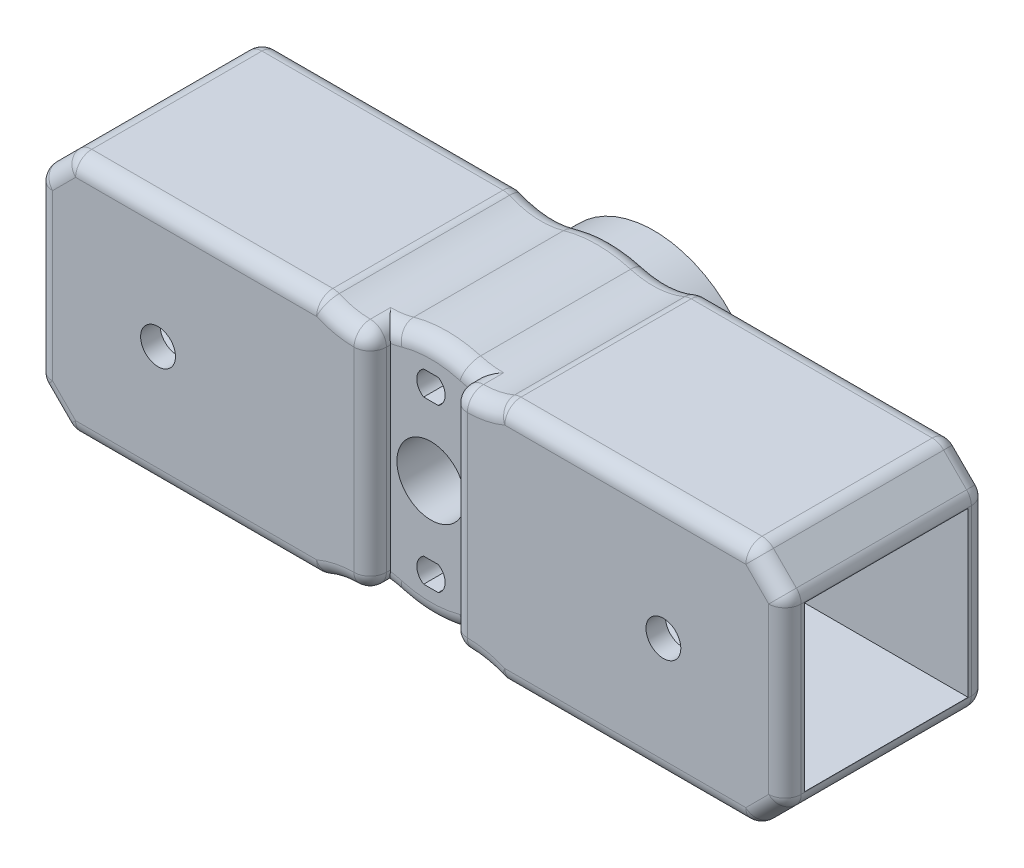
SolidWorks part; units mm, degrees
ref_plane "Alzado" through (0, 0, 0) normal (0, 0, 1) x (1, 0, 0)
ref_plane "Planta" through (0, 0, 0) normal (0, 1, 0) x (1, 0, 0)
ref_plane "Vista lateral" through (0, 0, 0) normal (1, 0, 0) x (0, 0, -1)
sketch "Croquis1" plane through (0, 0, 0) normal (0, 0, 1) x (1, 0, 0)
  circle A0 centre (0, 0) radius 15
  circle A1 centre (0, 0) radius 11.1
  dimension "D1" = 30
  dimension "D2" = 22.2
extrude "Saliente-Extruir1" add sketch "Croquis1" along normal mid plane 25
sketch "Croquis10" plane through (0, 0, 12.5) normal (0, 0, 1) x (1, 0, 0)
  line L0 (11.1803, 0) -> (-11.1803, 0) construction
  line L1 (0, 0) -> (0, 10.6419) construction
  line L2 (-11.1803, -15) -> (-11.1803, 15)
  line L3 (-11.1803, 15) -> (-46.1803, 15)
  line L4 (-46.1803, 15) -> (-46.1803, -15)
  line L5 (-46.1803, -15) -> (-11.1803, -15)
  line L6 (46.1803, 15) -> (46.1803, -15)
  line L7 (11.1803, 15) -> (46.1803, 15)
  line L8 (11.1803, -15) -> (11.1803, 15)
  line L9 (46.1803, -15) -> (11.1803, -15)
  line L10 (-11.1803, 0) -> (-46.1803, 0) construction
  circle A1 centre (-31.1803, 0) radius 2.15
  circle A2 centre (31.1803, 0) radius 2.15
  point P5 (0, 0)
  point P13 (-11.1803, 0)
  dimension "D3" = 4.3
  dimension "D1" = 35
  dimension "D2" = 30
  dimension "D4" = 15
extrude "Saliente-Extruir8" add sketch "Croquis10" against normal blind 25
sketch "Croquis11" plane through (0, 0, -12.5) normal (0, 0, 1) x (1, 0, 0)
  line L6 (0, 0) -> (0, 7.4469) construction
  line L7 (16.1803, -10) -> (36.1803, -10)
  line L8 (16.1803, 10) -> (16.1803, -10)
  line L9 (36.1803, 10) -> (16.1803, 10)
  line L10 (36.1803, -10) -> (36.1803, 10)
  dimension "D1" = 20
extrude "Cortar-Extruir1" [suppressed] cut sketch "Croquis11" along normal blind 10
sketch "Croquis12" plane through (0, 0, 12.5) normal (0, 0, 1) x (1, 0, 0)
  line L0 (-46.1803, 15) -> (-26.1803, 15)
  line L1 (-11.1803, 15) -> (-46.1803, 15) construction
  line L2 (-26.1803, 15) -> (-26.1803, -15)
  line L3 (-46.1803, -15) -> (-11.1803, -15) construction
  line L4 (-26.1803, -15) -> (-46.1803, -15)
  line L5 (-46.1803, -15) -> (-46.1803, 15)
  dimension "D1" = 20
extrude "Cortar-Extruir2" [suppressed] cut sketch "Croquis12" against normal blind 10
sketch "Croquis13" plane through (0, 0, 12.5) normal (0, 0, 1) x (1, 0, 0)
  circle A0 centre (0, 0) radius 11.1
  circle A1 centre (0, 0) radius 4.2
  dimension "D1" = 22.2
  dimension "D2" = 8.4
extrude "Saliente-Extruir9" add sketch "Croquis13" against normal blind 12.8
sketch "Croquis14" plane through (0, 0, -12.5) normal (0, 0, -1) x (-1, 0, 0)
  circle A0 centre (0, 0) radius 11.1
  circle A1 centre (0, 0) radius 13
  dimension "D1" = 22.2
  dimension "D2" = 26
extrude "Saliente-Extruir10" add sketch "Croquis14" along normal blind 5
sketch "Croquis15" plane through (0, 0, 12.5) normal (0, 0, 1) x (1, 0, 0)
  line L0 (-5, 0) -> (-5, 15)
  line L1 (-5, 15) -> (5, 15)
  line L2 (5, 15) -> (5, -15)
  line L3 (5, -15) -> (-5, -15)
  line L4 (-5, -15) -> (-5, 0)
  point P3 (0, 15)
  dimension "D1" = 10
  dimension "D2" = 30
extrude "Cortar-Extruir3" cut sketch "Croquis15" against normal blind 2.5
sketch "Croquis16" plane through (0, 0, 10) normal (0, 0, 1) x (1, 0, 0)
  line L0 (0, 15) -> (0, 10) construction
  line L1 (0, 10) -> (0, 0) construction
  line L2 (0, 0) -> (0, -10) construction
  line L3 (0, -10) -> (0, -15) construction
  line L4 (-0.9014, 11.5) -> (0.9014, 11.5)
  line L5 (-0.9014, 8.5) -> (0.9014, 8.5)
  line L6 (0, 0) -> (-3.0161, 0) construction
  line L7 (-0.9014, -8.5) -> (0.9014, -8.5)
  line L8 (-0.9014, -11.5) -> (0.9014, -11.5)
  arc A0 (5, 14.1421) -> (-5, 14.1421) centre (0, 0) ccw construction
  arc A1 (-5, -14.1421) -> (5, -14.1421) centre (0, 0) ccw construction
  arc A2 (-0.9014, 11.5) -> (-0.9014, 8.5) centre (0, 10) ccw
  arc A3 (0.9014, 8.5) -> (0.9014, 11.5) centre (0, 10) ccw
  arc A4 (-0.9014, -11.5) -> (-0.9014, -8.5) centre (0, -10) cw
  arc A5 (0.9014, -8.5) -> (0.9014, -11.5) centre (0, -10) cw
  point P16 (0, 11.5)
  point P19 (0, 8.5)
  dimension "D2" = 3.5
  dimension "D1" = 5
  dimension "D3" = 3
extrude "Cortar-Extruir4" cut sketch "Croquis16" against normal blind 7.5
sketch "Croquis17" plane through (-46.1803, 0, 0) normal (-1, 0, 0) x (0, 0, 1)
  line L1 (10.1, 10.1) -> (-10.1, 10.1)
  line L2 (10.1, 10.1) -> (10.1, -10.1)
  line L3 (10.1, -10.1) -> (-10.1, -10.1)
  line L4 (-10.1, 10.1) -> (-10.1, -10.1)
  line L5 (10.1, 10.1) -> (-10.1, -10.1) construction
  line L6 (10.1, -10.1) -> (-10.1, 10.1) construction
  point P0 (0, 0)
  dimension "D1" = 20.2
  dimension "D2" = 20.2
extrude "Cortar-Extruir5" cut sketch "Croquis17" against normal blind 30
mirror "Simetría1" about plane through (0, 0, 0) normal (1, 0, 0) of "Cortar-Extruir5"
fillet "Redondeo1" radius 10 4 edges at (-11.1803, 10, 0) (11.1803, 10, 0) (-11.1803, -10, 0) (11.1803, -10, 0)
chamfer "Chaflán1" distance 4 angle 45 4 edges at (46.1803, 15, 0) (46.1803, -15, 0) (-46.1803, 15, 0) (-46.1803, -15, 0)
fillet "Redondeo2" radius 2 54 edges at (-42.1803, -15, 0) (-44.1803, -13, 12.5) (-26.6803, -15, 12.5) (-11.1803, -15, 0) (-26.6803, -15, -12.5) (-46.1803, -11, 0) (-44.1803, -13, -12.5) (-46.1803, 0, 12.5) (-8.1531, -14.1125, 12.5) (-5, -14.2122, 11.25) (-7.7098, -14.066, -12.5) (-46.1803, 0, -12.5) (-46.1803, 11, 0) (-44.1803, 13, 12.5) (-5, 0, 12.5) (-5, 14.2122, 11.25) (-4.5643, -14.3061, 10) (0, -15, -12.5) (-42.1803, 15, 0) (-44.1803, 13, -12.5) (-26.6803, 15, 12.5) (-8.1531, 14.1125, 12.5) (-4.5643, 14.3061, 10) (0, -15, 10) (7.7098, -14.066, -12.5) (-26.6803, 15, -12.5) (-11.1803, 15, 0) (0, 15, 10) (4.5643, -14.3061, 10) (11.1803, -15, 0) (26.6803, -15, -12.5) (-7.7098, 14.066, -12.5) (4.5643, 14.3061, 10) (8.1531, -14.1125, 12.5) (5, -14.2122, 11.25) (26.6803, -15, 12.5) (42.1803, -15, 0) (44.1803, -13, -12.5) (0, 15, -12.5) (5, 14.2122, 11.25) (5, 0, 12.5) (46.1803, -11, 0) (44.1803, -13, 12.5) (46.1803, 0, -12.5) (7.7098, 14.066, -12.5) (8.1531, 14.1125, 12.5) (11.1803, 15, 0) (46.1803, 0, 12.5) (46.1803, 11, 0) (44.1803, 13, -12.5) (26.6803, 15, -12.5) (26.6803, 15, 12.5) (44.1803, 13, 12.5) (42.1803, 15, 0)
